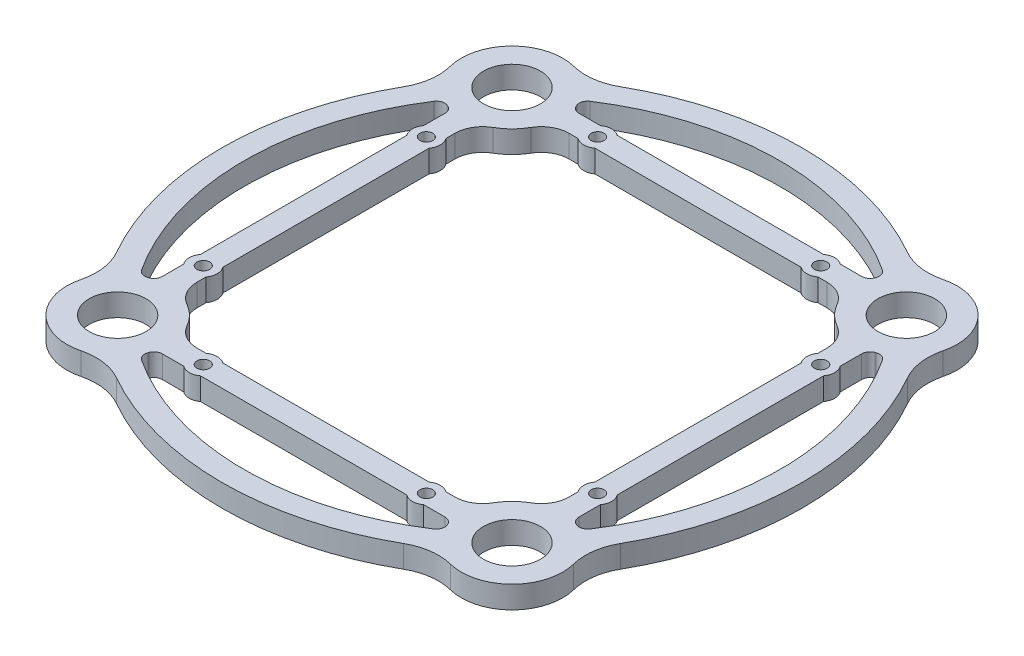
SolidWorks part; units mm, degrees
ref_plane "Front Plane" through (0, 0, 0) normal (0, 0, 1) x (1, 0, 0)
ref_plane "Top Plane" through (0, 0, 0) normal (0, 1, 0) x (1, 0, 0)
ref_plane "Right Plane" through (0, 0, 0) normal (1, 0, 0) x (0, 0, -1)
sketch "Sketch1" plane through (0, 0, 0) normal (0, 1, 0) x (1, 0, 0)
  line L1 (-35.3553, -35.3553) -> (35.3553, -35.3553) construction
  line L2 (-35.3553, -35.3553) -> (-35.3553, 35.3553) construction
  line L3 (-35.3553, 35.3553) -> (35.3553, 35.3553) construction
  line L4 (35.3553, -35.3553) -> (35.3553, 35.3553) construction
  line L5 (-35.3553, -35.3553) -> (35.3553, 35.3553) construction
  line L6 (-35.3553, 35.3553) -> (35.3553, -35.3553) construction
  circle A0 centre (0, 0) radius 52
  circle A1 centre (0, 0) radius 50 construction
  circle A2 centre (0, 0) radius 48
  circle A3 centre (35.3553, 35.3553) radius 5.1
  circle A4 centre (35.3553, 35.3553) radius 9.1
  circle A5 centre (-35.3553, 35.3553) radius 9.1
  circle A6 centre (-35.3553, 35.3553) radius 5.1
  circle A7 centre (-35.3553, -35.3553) radius 9.1
  circle A8 centre (-35.3553, -35.3553) radius 5.1
  circle A9 centre (35.3553, -35.3553) radius 5.1
  circle A10 centre (35.3553, -35.3553) radius 9.1
  dimension "D1" = 96
  dimension "D2" = 100
  dimension "D3" = 104
  dimension "D4" = 10.2
  dimension "D5" = 10.2
  dimension "D6" = 10.2
  dimension "D7" = 10.2
  dimension "D8" = 18.2
  dimension "D9" = 18.2
  dimension "D10" = 18.2
  dimension "D11" = 18.2
extrude "Boss-Extrude1" add sketch "Sketch1" along normal blind 4 contours A7 A2 A5 A0 | A5 A2 A4 A0 | A10 A0 A4 A2 | A10 A2 A7 A0 | A8 A2 A7 | A8 A2 A7 A0 | A8 A0 A7 | A8 A0 A7 A2 | A2 A10 A9 | A0 A10 A2 A9 | A0 A10 A9 | A2 A10 A0 A9 | A0 A4 A2 A3 | A2 A4 A0 A3 | A0 A4 A3 | A2 A4 A3 | A6 A2 A5 A0 | A6 A0 A5 A2 | A6 A0 A5 | A6 A2 A5 region at (49.0102, 0, 15.4585) region at (39.943, 0, -30.075) region at (39.073, 0, -39.073) region at (39.073, 0, 39.073) region at (39.943, 0, 30.075) region at (31.3721, 0, -31.3721) region at (31.3721, 0, 31.3721) region at (30.075, 0, -39.943) region at (0, 0, -48.6096) region at (30.075, 0, 39.943) region at (0, 0, 51.3904) region at (-31.3721, 0, -31.3721) region at (-30.075, 0, -39.943) region at (-39.073, 0, -39.073) region at (-39.073, 0, 39.073) region at (-30.075, 0, 39.943) region at (-31.3721, 0, 31.3721) region at (-41.5843, 0, -27.9071) region at (-39.943, 0, -30.075) region at (-39.943, 0, 30.075)
sketch "Sketch2" plane through (0, 4, 0) normal (0, 1, 0) x (1, 0, 0)
  line L0 (-33.3553, 26.4778) -> (-33.3553, -26.4778)
  line L1 (35.3553, -35.3553) -> (-35.3553, -35.3553) construction
  line L2 (35.3553, -35.3553) -> (35.3553, 35.3553) construction
  line L3 (35.3553, 35.3553) -> (-35.3553, 35.3553) construction
  line L4 (-35.3553, -35.3553) -> (-35.3553, 35.3553) construction
  line L5 (35.3553, -35.3553) -> (-35.3553, 35.3553) construction
  line L6 (35.3553, 35.3553) -> (-35.3553, -35.3553) construction
  line L7 (-37.3553, 26.4778) -> (-37.3553, -26.4778)
  line L8 (-26.4778, 37.3553) -> (26.4778, 37.3553)
  line L9 (-26.4778, 33.3553) -> (26.4778, 33.3553)
  line L10 (37.3553, 26.4778) -> (37.3553, -26.4778)
  line L11 (33.3553, 26.4778) -> (33.3553, -26.4778)
  line L12 (-26.4778, -33.3553) -> (26.4778, -33.3553)
  line L13 (-26.4778, -37.3553) -> (26.4778, -37.3553)
  arc A0 (-39.5091, 27.2586) -> (-27.2586, 39.5091) centre (-35.3553, 35.3553) ccw construction
  arc A1 (-27.2586, -39.5091) -> (-39.5091, -27.2586) centre (-35.3553, -35.3553) ccw construction
  arc A2 (27.2586, 39.5091) -> (39.5091, 27.2586) centre (35.3553, 35.3553) ccw construction
  arc A3 (39.5091, -27.2586) -> (27.2586, -39.5091) centre (35.3553, -35.3553) ccw construction
  circle A4 centre (-35.3553, 35.3553) radius 9.1
  circle A5 centre (35.3553, 35.3553) radius 9.1
  circle A6 centre (35.3553, -35.3553) radius 9.1
  circle A7 centre (-35.3553, -35.3553) radius 9.1
  point P0 (0, 0)
  arc M14 (-27.2586, -39.5091) -> (-39.5091, -27.2586) centre (-35.3553, -35.3553) ccw
  arc M16 (-39.5091, 27.2586) -> (-27.2586, 39.5091) centre (-35.3553, 35.3553) ccw
  arc M18 (27.2586, 39.5091) -> (39.5091, 27.2586) centre (35.3553, 35.3553) ccw
  arc M20 (39.5091, -27.2586) -> (27.2586, -39.5091) centre (35.3553, -35.3553) ccw
  dimension "D1" = 2
  dimension "D2" = 2
  dimension "D3" = 2
  dimension "D4" = 2
  dimension "D5" = 2
  dimension "D6" = 2
  dimension "D7" = 2
  dimension "D8" = 2
extrude "Boss-Extrude2" add sketch "Sketch2" against normal blind 4 contours L9 L8 M16 M18 | L7 L0 M16 M14 | L11 L10 M18 M20 | L13 L12 M14 M20 region at (-35.3553, 4, 0) region at (0, 4, -35.3553) region at (0, 4, 35.3553) region at (35.3553, 4, 0)
sketch "Sketch3" plane through (0, 4, 0) normal (0, 1, 0) x (1, 0, 0)
  line L0 (-26.4778, 33.3553) -> (26.4778, 33.3553) construction
  line L1 (-35.3553, 20) -> (35.3553, 20) construction
  line L2 (-35.3553, 20) -> (-35.3553, -20) construction
  line L3 (-35.3553, -20) -> (35.3553, -20) construction
  line L4 (35.3553, 20) -> (35.3553, -20) construction
  line L5 (-35.3553, 20) -> (35.3553, -20) construction
  line L6 (-35.3553, -20) -> (35.3553, 20) construction
  line L7 (20, -35.3553) -> (-20, -35.3553) construction
  line L8 (20, -35.3553) -> (20, 35.3553) construction
  line L9 (20, 35.3553) -> (-20, 35.3553) construction
  line L10 (-20, -35.3553) -> (-20, 35.3553) construction
  line L11 (20, -35.3553) -> (-20, 35.3553) construction
  line L12 (20, 35.3553) -> (-20, -35.3553) construction
  line L13 (-33.3553, 26.4778) -> (-33.3553, -26.4778) construction
  circle A0 centre (-20, 35.3553) radius 2.5
  circle A1 centre (20, 35.3553) radius 2.5
  circle A2 centre (35.3553, 20) radius 2.5
  circle A3 centre (35.3553, -20) radius 2.5
  circle A4 centre (-35.3553, -20) radius 2.5
  circle A5 centre (-35.3553, 20) radius 2.5
  circle A6 centre (-20, -35.3553) radius 2.5
  circle A7 centre (20, -35.3553) radius 2.5
  point P0 (0, 0)
  point P6 (0, 0)
  dimension "D5" = 5
  dimension "D6" = 5
  dimension "D7" = 5
  dimension "D8" = 5
  dimension "D9" = 5
  dimension "D10" = 5
  dimension "D11" = 5
  dimension "D12" = 5
  dimension "D1" = 2
  dimension "D2" = 2
  dimension "D3" = 40
  dimension "D4" = 40
extrude "Boss-Extrude3" add sketch "Sketch3" against normal blind 4
sketch "Sketch4" plane through (0, 4, 0) normal (0, 1, 0) x (1, 0, 0)
  circle A0 centre (-20, 35.3553) radius 1.15
  circle A1 centre (20, 35.3553) radius 1.15
  circle A2 centre (-35.3553, 20) radius 1.15
  circle A3 centre (-35.3553, -20) radius 1.15
  circle A4 centre (-20, -35.3553) radius 1.15
  circle A5 centre (20, -35.3553) radius 1.15
  circle A6 centre (35.3553, -20) radius 1.15
  circle A7 centre (35.3553, 20) radius 1.15
  dimension "D1" = 2.3
  dimension "D2" = 2.3
  dimension "D3" = 2.3
  dimension "D4" = 2.3
  dimension "D5" = 2.3
  dimension "D6" = 2.3
  dimension "D7" = 2.3
  dimension "D8" = 2.3
extrude "Cut-Extrude1" cut sketch "Sketch4" against normal blind 4
fillet "Fillet1" radius 10 8 edges at (29.8349, 2, 42.5896) (42.5896, 2, 29.8349) (42.5896, 2, -29.8349) (29.8349, 2, -42.5896) (-29.8349, 2, -42.5896) (-42.5896, 2, -29.8349) (-42.5896, 2, 29.8349) (-29.8349, 2, 42.5896)
fillet "Fillet2" radius 1.5 16 edges at (-39.5091, 2, 27.2586) (-37.3553, 2, 26.4778) (-39.5091, 2, -27.2586) (-37.3553, 2, -26.4778) (27.2586, 2, -39.5091) (26.4778, 2, -37.3553) (-26.4778, 2, -37.3553) (-27.2586, 2, -39.5091) (39.5091, 2, 27.2586) (37.3553, 2, 26.4778) (37.3553, 2, -26.4778) (39.5091, 2, -27.2586) (27.2586, 2, 39.5091) (26.4778, 2, 37.3553) (-27.2586, 2, 39.5091) (-26.4778, 2, 37.3553)
fillet "Fillet3" radius 5 8 edges at (-26.4778, 2, -33.3553) (-33.3553, 2, -26.4778) (-33.3553, 2, 26.4778) (-26.4778, 2, 33.3553) (26.4778, 2, 33.3553) (33.3553, 2, 26.4778) (26.4778, 2, -33.3553) (33.3553, 2, -26.4778)
